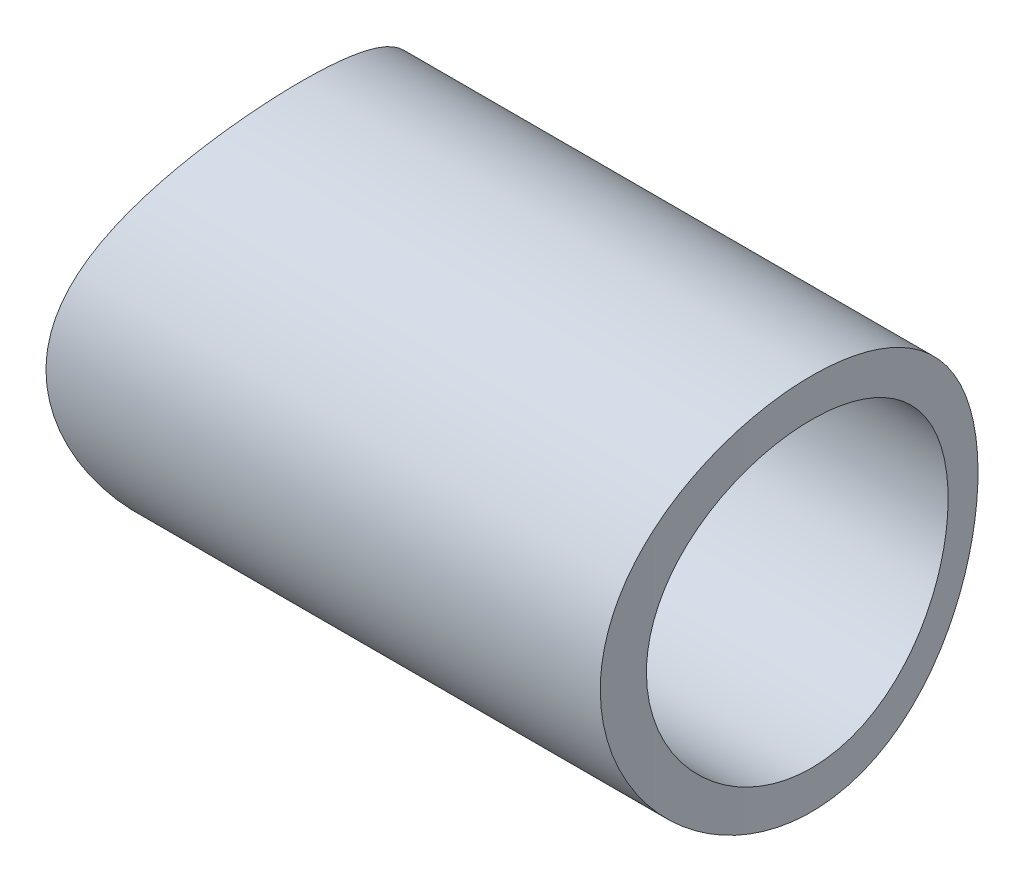
SolidWorks part; units mm, degrees
material "PTFE (general)"
ref_plane "Front Plane" through (0, 0, 0) normal (0, 0, 1) x (1, 0, 0)
ref_plane "Top Plane" through (0, 0, 0) normal (0, 1, 0) x (1, 0, 0)
ref_plane "Right Plane" through (0, 0, 0) normal (1, 0, 0) x (0, 0, -1)
sketch "Sketch1" plane through (0, 0, 0) normal (0, 1, 0) x (1, 0, 0)
  circle A0 centre (0, 0) radius 42.725
  circle A1 centre (0, 0) radius 15.875
  dimension "D1" = 31.75
  dimension "D2" = 85.45
extrude "Boss-Extrude1" add sketch "Sketch1" along normal blind 1
sketch "Sketch2" plane through (0, 1, 0) normal (0, 1, 0) x (1, 0, 0)
  circle A0 centre (0, 0) radius 16.875
  circle A1 centre (0, 0) radius 15.875
  circle A2 centre (0, 0) radius 42.725
  circle A3 centre (0, 0) radius 41.725
  circle A4 centre (0, 0) radius 15.875 construction
  circle A5 centre (0, 0) radius 42.725 construction
  dimension "D1" = 0
  dimension "D2" = 1
  dimension "D3" = 0
  dimension "D4" = 1
extrude "Boss-Extrude2" add sketch "Sketch2" along normal blind 25 contours A2 | A1 | A0 | A3
sketch "Sketch3" plane through (0, 0, 0) normal (1, 0, 0) x (0, 0, -1)
  line L1 (-42.725, 0) -> (42.725, 0) construction
  circle A1 centre (0, 11) radius 7.94
  dimension "D1" = 11
  dimension "D2" = 15.88
extrude "Cut-Extrude1" cut sketch "Sketch3" along normal through all
sketch "Sketch9" plane through (0, 0, 0) normal (1, 0, 0) x (0, 0, -1)
  circle A0 centre (0, 11) radius 9.94
  circle A1 centre (0, 11) radius 7.94
  dimension "D1" = 2
  dimension "D2" = 15.88
extrude "Boss-Extrude3" add sketch "Sketch9" along normal up to surface (41.5526 mm away) up to face at (0, 0, 42.725)
sketch "Sketch10" plane through (0, 26, 0) normal (0, 1, 0) x (1, 0, 0)
  line L5 (0, 9.94) -> (0, -9.94) construction
  line L10 (1.5624, 15.7979) -> (41.0361, 11.894)
  line L11 (1.5624, -15.7979) -> (41.0361, -11.894)
  circle A3 centre (0, 0) radius 15.875 construction
  circle A4 centre (0, 0) radius 15.875
  circle A5 centre (0, 0) radius 42.725
  circle A6 centre (0, 0) radius 42.725 construction
  circle M1 centre (0, 0) radius 16.875
  circle M2 centre (0, 0) radius 15.875
  dimension "D2" = 0
  dimension "D1" = 0
extrude "Cut-Extrude2" cut sketch "Sketch10" against normal through all both and the other way through all contours M2 | L11 L10 M2 M1 | L10 A5 L11 M1 | A4 region at (-16.2899, 26, 0) region at (0, 26, 0) region at (-18.0716, 26, 0)
sketch "Sketch11" plane through (0, 0, 0) normal (1, 0, 0) x (0, 0, -1)
  circle A0 centre (0, 11) radius 9.94
  circle A2 centre (0, 11) radius 50
  circle A3 centre (0, 11) radius 7.94 construction
  dimension "D1" = 2
  dimension "D2" = 100
extrude "Cut-Extrude4" cut sketch "Sketch11" along normal through all both and the other way through all
